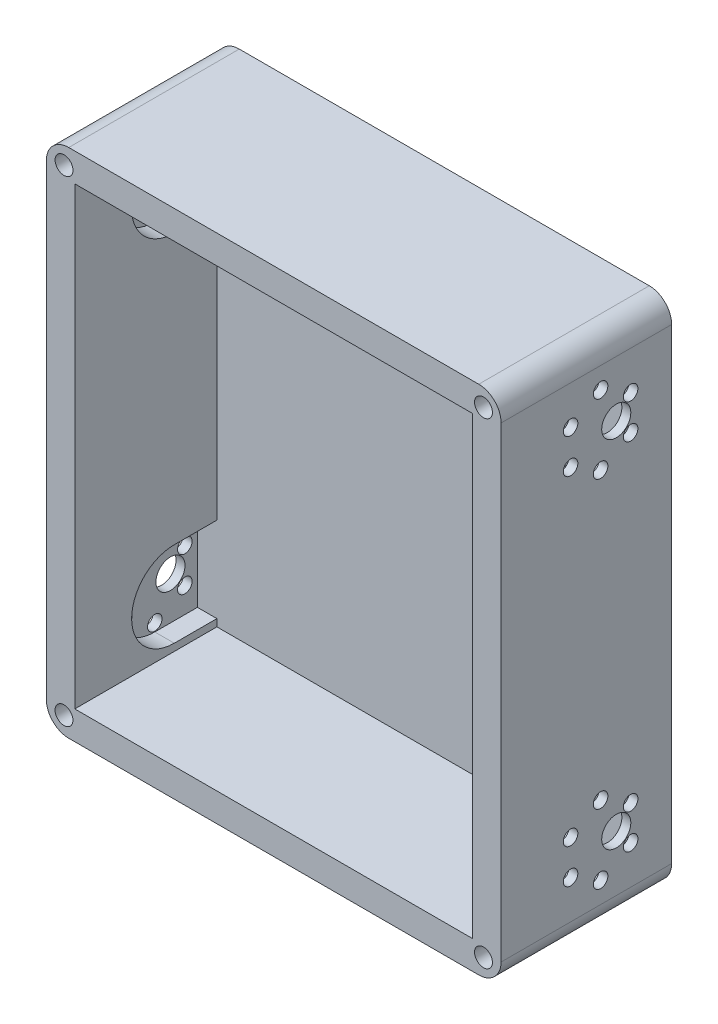
SolidWorks part; units mm, degrees
material "ABS"
ref_plane "Front Plane" through (0, 0, 0) normal (0, 0, 1) x (1, 0, 0)
ref_plane "Top Plane" through (0, 0, 0) normal (0, 1, 0) x (1, 0, 0)
ref_plane "Right Plane" through (0, 0, 0) normal (1, 0, 0) x (0, 0, -1)
sketch "Sketch1" plane through (0, 0, 0) normal (0, 0, 1) x (1, 0, 0)
  line L1 (-106.7309, 50.6092) -> (96.4691, 50.6092)
  line L2 (-106.7309, 50.6092) -> (-106.7309, -177.9908)
  line L3 (-106.7309, -177.9908) -> (96.4691, -177.9908)
  line L4 (96.4691, 50.6092) -> (96.4691, -177.9908)
  dimension "D1" = 203.2
  dimension "D2" = 228.6
extrude "Chassis" add sketch "Sketch1" along normal blind 76.2
shell "Chassis Compartment" thickness 12.7 removed face at (-5.1309, -63.6908, 76.2)
fillet "Outer Fillets" radius 10 4 edges at (96.4691, 50.6092, 38.1) (-106.7309, 50.6092, 38.1) (-106.7309, -177.9908, 38.1) (96.4691, -177.9908, 38.1)
ref_plane "Bottom Plane - Inner" through (0, 0, 12.7) normal (0, 0, 1) x (1, 0, 0)
sketch "Sketch2" plane through (0, 0, 12.7) normal (0, 0, 1) x (1, 0, 0)
  line L0 (-307.7698, 96.8742) -> (-323.3628, 77.6984)
  line L1 (-323.3628, 77.6984) -> (-308.8421, 57.6984)
  line L2 (-308.8421, 57.6984) -> (-293.2492, 76.8742)
  line L3 (-293.2492, 76.8742) -> (-307.7698, 96.8742)
  line L4 (-267.7698, 96.8742) -> (-283.3628, 77.6984)
  line L5 (-283.3628, 77.6984) -> (-268.8421, 57.6984)
  line L6 (-268.8421, 57.6984) -> (-253.2492, 76.8742)
  line L7 (-253.2492, 76.8742) -> (-267.7698, 96.8742)
  line L8 (-227.7698, 96.8742) -> (-243.3628, 77.6984)
  line L9 (-243.3628, 77.6984) -> (-228.8421, 57.6984)
  line L10 (-228.8421, 57.6984) -> (-213.2492, 76.8742)
  line L11 (-213.2492, 76.8742) -> (-227.7698, 96.8742)
  line L12 (-187.7698, 96.8742) -> (-203.3628, 77.6984)
  line L13 (-203.3628, 77.6984) -> (-188.8421, 57.6984)
  line L14 (-188.8421, 57.6984) -> (-173.2492, 76.8742)
  line L15 (-173.2492, 76.8742) -> (-187.7698, 96.8742)
  line L16 (-147.7698, 96.8742) -> (-163.3628, 77.6984)
  line L17 (-163.3628, 77.6984) -> (-148.8421, 57.6984)
  line L18 (-148.8421, 57.6984) -> (-133.2492, 76.8742)
  line L19 (-133.2492, 76.8742) -> (-147.7698, 96.8742)
  line L20 (-107.7698, 96.8742) -> (-123.3628, 77.6984)
  line L21 (-123.3628, 77.6984) -> (-108.8421, 57.6984)
  line L22 (-108.8421, 57.6984) -> (-93.2492, 76.8742)
  line L23 (-93.2492, 76.8742) -> (-107.7698, 96.8742)
  line L24 (-67.7698, 96.8742) -> (-83.3628, 77.6984)
  line L25 (-83.3628, 77.6984) -> (-68.8421, 57.6984)
  line L26 (-68.8421, 57.6984) -> (-53.2492, 76.8742)
  line L27 (-53.2492, 76.8742) -> (-67.7698, 96.8742)
  line L28 (-27.7698, 96.8742) -> (-43.3628, 77.6984)
  line L29 (-43.3628, 77.6984) -> (-28.8421, 57.6984)
  line L30 (-28.8421, 57.6984) -> (-13.2492, 76.8742)
  line L31 (-13.2492, 76.8742) -> (-27.7698, 96.8742)
  line L32 (12.2302, 96.8742) -> (-3.3628, 77.6984)
  line L33 (-3.3628, 77.6984) -> (11.1579, 57.6984)
  line L34 (11.1579, 57.6984) -> (26.7508, 76.8742)
  line L35 (26.7508, 76.8742) -> (12.2302, 96.8742)
  line L36 (52.2302, 96.8742) -> (36.6372, 77.6984)
  line L37 (36.6372, 77.6984) -> (51.1579, 57.6984)
  line L38 (51.1579, 57.6984) -> (66.7508, 76.8742)
  line L39 (66.7508, 76.8742) -> (52.2302, 96.8742)
  line L40 (92.2302, 96.8742) -> (76.6372, 77.6984)
  line L41 (76.6372, 77.6984) -> (91.1579, 57.6984)
  line L42 (91.1579, 57.6984) -> (106.7508, 76.8742)
  line L43 (106.7508, 76.8742) -> (92.2302, 96.8742)
  line L44 (132.2302, 96.8742) -> (116.6372, 77.6984)
  line L45 (116.6372, 77.6984) -> (131.1579, 57.6984)
  line L46 (131.1579, 57.6984) -> (146.7508, 76.8742)
  line L47 (146.7508, 76.8742) -> (132.2302, 96.8742)
  line L48 (172.2302, 96.8742) -> (156.6372, 77.6984)
  line L49 (156.6372, 77.6984) -> (171.1579, 57.6984)
  line L50 (171.1579, 57.6984) -> (186.7508, 76.8742)
  line L51 (186.7508, 76.8742) -> (172.2302, 96.8742)
  line L52 (212.2302, 96.8742) -> (196.6372, 77.6984)
  line L53 (196.6372, 77.6984) -> (211.1579, 57.6984)
  line L54 (211.1579, 57.6984) -> (226.7508, 76.8742)
  line L55 (226.7508, 76.8742) -> (212.2302, 96.8742)
  line L56 (252.2302, 96.8742) -> (236.6372, 77.6984)
  line L57 (236.6372, 77.6984) -> (251.1579, 57.6984)
  line L58 (251.1579, 57.6984) -> (266.7508, 76.8742)
  line L59 (266.7508, 76.8742) -> (252.2302, 96.8742)
  line L60 (-245.9843, 63.3274) -> (-261.5772, 44.1516)
  line L61 (-261.5772, 44.1516) -> (-247.0565, 24.1516)
  line L62 (-247.0565, 24.1516) -> (-231.4636, 43.3274)
  line L63 (-231.4636, 43.3274) -> (-245.9843, 63.3274)
  line L64 (-205.9843, 63.3274) -> (-221.5772, 44.1516)
  line L65 (-221.5772, 44.1516) -> (-207.0565, 24.1516)
  line L66 (-207.0565, 24.1516) -> (-191.4636, 43.3274)
  line L67 (-191.4636, 43.3274) -> (-205.9843, 63.3274)
  line L68 (-165.9843, 63.3274) -> (-181.5772, 44.1516)
  line L69 (-181.5772, 44.1516) -> (-167.0565, 24.1516)
  line L70 (-167.0565, 24.1516) -> (-151.4636, 43.3274)
  line L71 (-151.4636, 43.3274) -> (-165.9843, 63.3274)
  line L72 (-125.9843, 63.3274) -> (-141.5772, 44.1516)
  line L73 (-141.5772, 44.1516) -> (-127.0565, 24.1516)
  line L74 (-127.0565, 24.1516) -> (-111.4636, 43.3274)
  line L75 (-111.4636, 43.3274) -> (-125.9843, 63.3274)
  line L76 (-85.9843, 63.3274) -> (-101.5772, 44.1516)
  line L77 (-101.5772, 44.1516) -> (-87.0565, 24.1516)
  line L78 (-87.0565, 24.1516) -> (-71.4636, 43.3274)
  line L79 (-71.4636, 43.3274) -> (-85.9843, 63.3274)
  line L80 (-45.9843, 63.3274) -> (-61.5772, 44.1516)
  line L81 (-61.5772, 44.1516) -> (-47.0565, 24.1516)
  line L82 (-47.0565, 24.1516) -> (-31.4636, 43.3274)
  line L83 (-31.4636, 43.3274) -> (-45.9843, 63.3274)
  line L84 (-5.9843, 63.3274) -> (-21.5772, 44.1516)
  line L85 (-21.5772, 44.1516) -> (-7.0565, 24.1516)
  line L86 (-7.0565, 24.1516) -> (8.5364, 43.3274)
  line L87 (8.5364, 43.3274) -> (-5.9843, 63.3274)
  line L88 (34.0157, 63.3274) -> (18.4228, 44.1516)
  line L89 (18.4228, 44.1516) -> (32.9435, 24.1516)
  line L90 (32.9435, 24.1516) -> (48.5364, 43.3274)
  line L91 (48.5364, 43.3274) -> (34.0157, 63.3274)
  line L92 (74.0157, 63.3274) -> (58.4228, 44.1516)
  line L93 (58.4228, 44.1516) -> (72.9435, 24.1516)
  line L94 (72.9435, 24.1516) -> (88.5364, 43.3274)
  line L95 (88.5364, 43.3274) -> (74.0157, 63.3274)
  line L96 (114.0157, 63.3274) -> (98.4228, 44.1516)
  line L97 (98.4228, 44.1516) -> (112.9435, 24.1516)
  line L98 (112.9435, 24.1516) -> (128.5364, 43.3274)
  line L99 (128.5364, 43.3274) -> (114.0157, 63.3274)
  line L100 (154.0157, 63.3274) -> (138.4228, 44.1516)
  line L101 (138.4228, 44.1516) -> (152.9435, 24.1516)
  line L102 (152.9435, 24.1516) -> (168.5364, 43.3274)
  line L103 (168.5364, 43.3274) -> (154.0157, 63.3274)
  line L104 (194.0157, 63.3274) -> (178.4228, 44.1516)
  line L105 (178.4228, 44.1516) -> (192.9435, 24.1516)
  line L106 (192.9435, 24.1516) -> (208.5364, 43.3274)
  line L107 (208.5364, 43.3274) -> (194.0157, 63.3274)
  line L108 (234.0157, 63.3274) -> (218.4228, 44.1516)
  line L109 (218.4228, 44.1516) -> (232.9435, 24.1516)
  line L110 (232.9435, 24.1516) -> (248.5364, 43.3274)
  line L111 (248.5364, 43.3274) -> (234.0157, 63.3274)
  line L112 (274.0157, 63.3274) -> (258.4228, 44.1516)
  line L113 (258.4228, 44.1516) -> (272.9435, 24.1516)
  line L114 (272.9435, 24.1516) -> (288.5364, 43.3274)
  line L115 (288.5364, 43.3274) -> (274.0157, 63.3274)
  line L116 (-224.1987, 29.7805) -> (-239.7917, 10.6048)
  line L117 (-239.7917, 10.6048) -> (-225.271, -9.3952)
  line L118 (-225.271, -9.3952) -> (-209.678, 9.7805)
  line L119 (-209.678, 9.7805) -> (-224.1987, 29.7805)
  line L120 (-184.1987, 29.7805) -> (-199.7917, 10.6048)
  line L121 (-199.7917, 10.6048) -> (-185.271, -9.3952)
  line L122 (-185.271, -9.3952) -> (-169.678, 9.7805)
  line L123 (-169.678, 9.7805) -> (-184.1987, 29.7805)
  line L124 (-144.1987, 29.7805) -> (-159.7917, 10.6048)
  line L125 (-159.7917, 10.6048) -> (-145.271, -9.3952)
  line L126 (-145.271, -9.3952) -> (-129.678, 9.7805)
  line L127 (-129.678, 9.7805) -> (-144.1987, 29.7805)
  line L128 (-104.1987, 29.7805) -> (-119.7917, 10.6048)
  line L129 (-119.7917, 10.6048) -> (-105.271, -9.3952)
  line L130 (-105.271, -9.3952) -> (-89.678, 9.7805)
  line L131 (-89.678, 9.7805) -> (-104.1987, 29.7805)
  line L132 (-64.1987, 29.7805) -> (-79.7917, 10.6048)
  line L133 (-79.7917, 10.6048) -> (-65.271, -9.3952)
  line L134 (-65.271, -9.3952) -> (-49.678, 9.7805)
  line L135 (-49.678, 9.7805) -> (-64.1987, 29.7805)
  line L136 (-24.1987, 29.7805) -> (-39.7917, 10.6048)
  line L137 (-39.7917, 10.6048) -> (-25.271, -9.3952)
  line L138 (-25.271, -9.3952) -> (-9.678, 9.7805)
  line L139 (-9.678, 9.7805) -> (-24.1987, 29.7805)
  line L140 (15.8013, 29.7805) -> (0.2083, 10.6048)
  line L141 (0.2083, 10.6048) -> (14.729, -9.3952)
  line L142 (14.729, -9.3952) -> (30.322, 9.7805)
  line L143 (30.322, 9.7805) -> (15.8013, 29.7805)
  line L144 (55.8013, 29.7805) -> (40.2083, 10.6048)
  line L145 (40.2083, 10.6048) -> (54.729, -9.3952)
  line L146 (54.729, -9.3952) -> (70.322, 9.7805)
  line L147 (70.322, 9.7805) -> (55.8013, 29.7805)
  line L148 (95.8013, 29.7805) -> (80.2083, 10.6048)
  line L149 (80.2083, 10.6048) -> (94.729, -9.3952)
  line L150 (94.729, -9.3952) -> (110.322, 9.7805)
  line L151 (110.322, 9.7805) -> (95.8013, 29.7805)
  line L152 (135.8013, 29.7805) -> (120.2083, 10.6048)
  line L153 (120.2083, 10.6048) -> (134.729, -9.3952)
  line L154 (134.729, -9.3952) -> (150.322, 9.7805)
  line L155 (150.322, 9.7805) -> (135.8013, 29.7805)
  line L156 (175.8013, 29.7805) -> (160.2083, 10.6048)
  line L157 (160.2083, 10.6048) -> (174.729, -9.3952)
  line L158 (174.729, -9.3952) -> (190.322, 9.7805)
  line L159 (190.322, 9.7805) -> (175.8013, 29.7805)
  line L160 (215.8013, 29.7805) -> (200.2083, 10.6048)
  line L161 (200.2083, 10.6048) -> (214.729, -9.3952)
  line L162 (214.729, -9.3952) -> (230.322, 9.7805)
  line L163 (230.322, 9.7805) -> (215.8013, 29.7805)
  line L164 (255.8013, 29.7805) -> (240.2083, 10.6048)
  line L165 (240.2083, 10.6048) -> (254.729, -9.3952)
  line L166 (254.729, -9.3952) -> (270.322, 9.7805)
  line L167 (270.322, 9.7805) -> (255.8013, 29.7805)
  line L168 (295.8013, 29.7805) -> (280.2083, 10.6048)
  line L169 (280.2083, 10.6048) -> (294.729, -9.3952)
  line L170 (294.729, -9.3952) -> (310.322, 9.7805)
  line L171 (310.322, 9.7805) -> (295.8013, 29.7805)
  line L172 (-202.4132, -3.7663) -> (-218.0061, -22.9421)
  line L173 (-218.0061, -22.9421) -> (-203.4854, -42.9421)
  line L174 (-203.4854, -42.9421) -> (-187.8925, -23.7663)
  line L175 (-187.8925, -23.7663) -> (-202.4132, -3.7663)
  line L176 (-162.4132, -3.7663) -> (-178.0061, -22.9421)
  line L177 (-178.0061, -22.9421) -> (-163.4854, -42.9421)
  line L178 (-163.4854, -42.9421) -> (-147.8925, -23.7663)
  line L179 (-147.8925, -23.7663) -> (-162.4132, -3.7663)
  line L180 (-122.4132, -3.7663) -> (-138.0061, -22.9421)
  line L181 (-138.0061, -22.9421) -> (-123.4854, -42.9421)
  line L182 (-123.4854, -42.9421) -> (-107.8925, -23.7663)
  line L183 (-107.8925, -23.7663) -> (-122.4132, -3.7663)
  line L184 (-82.4132, -3.7663) -> (-98.0061, -22.9421)
  line L185 (-98.0061, -22.9421) -> (-83.4854, -42.9421)
  line L186 (-83.4854, -42.9421) -> (-67.8925, -23.7663)
  line L187 (-67.8925, -23.7663) -> (-82.4132, -3.7663)
  line L188 (-42.4132, -3.7663) -> (-58.0061, -22.9421)
  line L189 (-58.0061, -22.9421) -> (-43.4854, -42.9421)
  line L190 (-43.4854, -42.9421) -> (-27.8925, -23.7663)
  line L191 (-27.8925, -23.7663) -> (-42.4132, -3.7663)
  line L192 (-2.4132, -3.7663) -> (-18.0061, -22.9421)
  line L193 (-18.0061, -22.9421) -> (-3.4854, -42.9421)
  line L194 (-3.4854, -42.9421) -> (12.1075, -23.7663)
  line L195 (12.1075, -23.7663) -> (-2.4132, -3.7663)
  line L196 (37.5868, -3.7663) -> (21.9939, -22.9421)
  line L197 (21.9939, -22.9421) -> (36.5146, -42.9421)
  line L198 (36.5146, -42.9421) -> (52.1075, -23.7663)
  line L199 (52.1075, -23.7663) -> (37.5868, -3.7663)
  line L200 (77.5868, -3.7663) -> (61.9939, -22.9421)
  line L201 (61.9939, -22.9421) -> (76.5146, -42.9421)
  line L202 (76.5146, -42.9421) -> (92.1075, -23.7663)
  line L203 (92.1075, -23.7663) -> (77.5868, -3.7663)
  line L204 (117.5868, -3.7663) -> (101.9939, -22.9421)
  line L205 (101.9939, -22.9421) -> (116.5146, -42.9421)
  line L206 (116.5146, -42.9421) -> (132.1075, -23.7663)
  line L207 (132.1075, -23.7663) -> (117.5868, -3.7663)
  line L208 (157.5868, -3.7663) -> (141.9939, -22.9421)
  line L209 (141.9939, -22.9421) -> (156.5146, -42.9421)
  line L210 (156.5146, -42.9421) -> (172.1075, -23.7663)
  line L211 (172.1075, -23.7663) -> (157.5868, -3.7663)
  line L212 (197.5868, -3.7663) -> (181.9939, -22.9421)
  line L213 (181.9939, -22.9421) -> (196.5146, -42.9421)
  line L214 (196.5146, -42.9421) -> (212.1075, -23.7663)
  line L215 (212.1075, -23.7663) -> (197.5868, -3.7663)
  line L216 (237.5868, -3.7663) -> (221.9939, -22.9421)
  line L217 (221.9939, -22.9421) -> (236.5146, -42.9421)
  line L218 (236.5146, -42.9421) -> (252.1075, -23.7663)
  line L219 (252.1075, -23.7663) -> (237.5868, -3.7663)
  line L220 (277.5868, -3.7663) -> (261.9939, -22.9421)
  line L221 (261.9939, -22.9421) -> (276.5146, -42.9421)
  line L222 (276.5146, -42.9421) -> (292.1075, -23.7663)
  line L223 (292.1075, -23.7663) -> (277.5868, -3.7663)
  line L224 (317.5868, -3.7663) -> (301.9939, -22.9421)
  line L225 (301.9939, -22.9421) -> (316.5146, -42.9421)
  line L226 (316.5146, -42.9421) -> (332.1075, -23.7663)
  line L227 (332.1075, -23.7663) -> (317.5868, -3.7663)
  line L228 (-180.6276, -37.3131) -> (-196.2206, -56.4889)
  line L229 (-196.2206, -56.4889) -> (-181.6999, -76.4889)
  line L230 (-181.6999, -76.4889) -> (-166.1069, -57.3131)
  line L231 (-166.1069, -57.3131) -> (-180.6276, -37.3131)
  line L232 (-140.6276, -37.3131) -> (-156.2206, -56.4889)
  line L233 (-156.2206, -56.4889) -> (-141.6999, -76.4889)
  line L234 (-141.6999, -76.4889) -> (-126.1069, -57.3131)
  line L235 (-126.1069, -57.3131) -> (-140.6276, -37.3131)
  line L236 (-100.6276, -37.3131) -> (-116.2206, -56.4889)
  line L237 (-116.2206, -56.4889) -> (-101.6999, -76.4889)
  line L238 (-101.6999, -76.4889) -> (-86.1069, -57.3131)
  line L239 (-86.1069, -57.3131) -> (-100.6276, -37.3131)
  line L240 (-60.6276, -37.3131) -> (-76.2206, -56.4889)
  line L241 (-76.2206, -56.4889) -> (-61.6999, -76.4889)
  line L242 (-61.6999, -76.4889) -> (-46.1069, -57.3131)
  line L243 (-46.1069, -57.3131) -> (-60.6276, -37.3131)
  line L244 (-20.6276, -37.3131) -> (-36.2206, -56.4889)
  line L245 (-36.2206, -56.4889) -> (-21.6999, -76.4889)
  line L246 (-21.6999, -76.4889) -> (-6.1069, -57.3131)
  line L247 (-6.1069, -57.3131) -> (-20.6276, -37.3131)
  line L248 (19.3724, -37.3131) -> (3.7794, -56.4889)
  line L249 (3.7794, -56.4889) -> (18.3001, -76.4889)
  line L250 (18.3001, -76.4889) -> (33.8931, -57.3131)
  line L251 (33.8931, -57.3131) -> (19.3724, -37.3131)
  line L252 (59.3724, -37.3131) -> (43.7794, -56.4889)
  line L253 (43.7794, -56.4889) -> (58.3001, -76.4889)
  line L254 (58.3001, -76.4889) -> (73.8931, -57.3131)
  line L255 (73.8931, -57.3131) -> (59.3724, -37.3131)
  line L256 (99.3724, -37.3131) -> (83.7794, -56.4889)
  line L257 (83.7794, -56.4889) -> (98.3001, -76.4889)
  line L258 (98.3001, -76.4889) -> (113.8931, -57.3131)
  line L259 (113.8931, -57.3131) -> (99.3724, -37.3131)
  line L260 (139.3724, -37.3131) -> (123.7794, -56.4889)
  line L261 (123.7794, -56.4889) -> (138.3001, -76.4889)
  line L262 (138.3001, -76.4889) -> (153.8931, -57.3131)
  line L263 (153.8931, -57.3131) -> (139.3724, -37.3131)
  line L264 (179.3724, -37.3131) -> (163.7794, -56.4889)
  line L265 (163.7794, -56.4889) -> (178.3001, -76.4889)
  line L266 (178.3001, -76.4889) -> (193.8931, -57.3131)
  line L267 (193.8931, -57.3131) -> (179.3724, -37.3131)
  line L268 (219.3724, -37.3131) -> (203.7794, -56.4889)
  line L269 (203.7794, -56.4889) -> (218.3001, -76.4889)
  line L270 (218.3001, -76.4889) -> (233.8931, -57.3131)
  line L271 (233.8931, -57.3131) -> (219.3724, -37.3131)
  line L272 (259.3724, -37.3131) -> (243.7794, -56.4889)
  line L273 (243.7794, -56.4889) -> (258.3001, -76.4889)
  line L274 (258.3001, -76.4889) -> (273.8931, -57.3131)
  line L275 (273.8931, -57.3131) -> (259.3724, -37.3131)
  line L276 (299.3724, -37.3131) -> (283.7794, -56.4889)
  line L277 (283.7794, -56.4889) -> (298.3001, -76.4889)
  line L278 (298.3001, -76.4889) -> (313.8931, -57.3131)
  line L279 (313.8931, -57.3131) -> (299.3724, -37.3131)
  line L280 (339.3724, -37.3131) -> (323.7794, -56.4889)
  line L281 (323.7794, -56.4889) -> (338.3001, -76.4889)
  line L282 (338.3001, -76.4889) -> (353.8931, -57.3131)
  line L283 (353.8931, -57.3131) -> (339.3724, -37.3131)
  line L284 (-158.842, -70.8599) -> (-174.435, -90.0357)
  line L285 (-174.435, -90.0357) -> (-159.9143, -110.0357)
  line L286 (-159.9143, -110.0357) -> (-144.3213, -90.8599)
  line L287 (-144.3213, -90.8599) -> (-158.842, -70.8599)
  line L288 (-118.842, -70.8599) -> (-134.435, -90.0357)
  line L289 (-134.435, -90.0357) -> (-119.9143, -110.0357)
  line L290 (-119.9143, -110.0357) -> (-104.3213, -90.8599)
  line L291 (-104.3213, -90.8599) -> (-118.842, -70.8599)
  line L292 (-78.842, -70.8599) -> (-94.435, -90.0357)
  line L293 (-94.435, -90.0357) -> (-79.9143, -110.0357)
  line L294 (-79.9143, -110.0357) -> (-64.3213, -90.8599)
  line L295 (-64.3213, -90.8599) -> (-78.842, -70.8599)
  line L296 (-38.842, -70.8599) -> (-54.435, -90.0357)
  line L297 (-54.435, -90.0357) -> (-39.9143, -110.0357)
  line L298 (-39.9143, -110.0357) -> (-24.3213, -90.8599)
  line L299 (-24.3213, -90.8599) -> (-38.842, -70.8599)
  line L300 (1.158, -70.8599) -> (-14.435, -90.0357)
  line L301 (-14.435, -90.0357) -> (0.0857, -110.0357)
  line L302 (0.0857, -110.0357) -> (15.6787, -90.8599)
  line L303 (15.6787, -90.8599) -> (1.158, -70.8599)
  line L304 (41.158, -70.8599) -> (25.565, -90.0357)
  line L305 (25.565, -90.0357) -> (40.0857, -110.0357)
  line L306 (40.0857, -110.0357) -> (55.6787, -90.8599)
  line L307 (55.6787, -90.8599) -> (41.158, -70.8599)
  line L308 (81.158, -70.8599) -> (65.565, -90.0357)
  line L309 (65.565, -90.0357) -> (80.0857, -110.0357)
  line L310 (80.0857, -110.0357) -> (95.6787, -90.8599)
  line L311 (95.6787, -90.8599) -> (81.158, -70.8599)
  line L312 (121.158, -70.8599) -> (105.565, -90.0357)
  line L313 (105.565, -90.0357) -> (120.0857, -110.0357)
  line L314 (120.0857, -110.0357) -> (135.6787, -90.8599)
  line L315 (135.6787, -90.8599) -> (121.158, -70.8599)
  line L316 (161.158, -70.8599) -> (145.565, -90.0357)
  line L317 (145.565, -90.0357) -> (160.0857, -110.0357)
  line L318 (160.0857, -110.0357) -> (175.6787, -90.8599)
  line L319 (175.6787, -90.8599) -> (161.158, -70.8599)
  line L320 (201.158, -70.8599) -> (185.565, -90.0357)
  line L321 (185.565, -90.0357) -> (200.0857, -110.0357)
  line L322 (200.0857, -110.0357) -> (215.6787, -90.8599)
  line L323 (215.6787, -90.8599) -> (201.158, -70.8599)
  line L324 (241.158, -70.8599) -> (225.565, -90.0357)
  line L325 (225.565, -90.0357) -> (240.0857, -110.0357)
  line L326 (240.0857, -110.0357) -> (255.6787, -90.8599)
  line L327 (255.6787, -90.8599) -> (241.158, -70.8599)
  line L328 (281.158, -70.8599) -> (265.565, -90.0357)
  line L329 (265.565, -90.0357) -> (280.0857, -110.0357)
  line L330 (280.0857, -110.0357) -> (295.6787, -90.8599)
  line L331 (295.6787, -90.8599) -> (281.158, -70.8599)
  line L332 (321.158, -70.8599) -> (305.565, -90.0357)
  line L333 (305.565, -90.0357) -> (320.0857, -110.0357)
  line L334 (320.0857, -110.0357) -> (335.6787, -90.8599)
  line L335 (335.6787, -90.8599) -> (321.158, -70.8599)
  line L336 (361.158, -70.8599) -> (345.565, -90.0357)
  line L337 (345.565, -90.0357) -> (360.0857, -110.0357)
  line L338 (360.0857, -110.0357) -> (375.6787, -90.8599)
  line L339 (375.6787, -90.8599) -> (361.158, -70.8599)
  line L340 (-137.0565, -104.4068) -> (-152.6494, -123.5825)
  line L341 (-152.6494, -123.5825) -> (-138.1287, -143.5825)
  line L342 (-138.1287, -143.5825) -> (-122.5358, -124.4068)
  line L343 (-122.5358, -124.4068) -> (-137.0565, -104.4068)
  line L344 (-97.0565, -104.4068) -> (-112.6494, -123.5825)
  line L345 (-112.6494, -123.5825) -> (-98.1287, -143.5825)
  line L346 (-98.1287, -143.5825) -> (-82.5358, -124.4068)
  line L347 (-82.5358, -124.4068) -> (-97.0565, -104.4068)
  line L348 (-57.0565, -104.4068) -> (-72.6494, -123.5825)
  line L349 (-72.6494, -123.5825) -> (-58.1287, -143.5825)
  line L350 (-58.1287, -143.5825) -> (-42.5358, -124.4068)
  line L351 (-42.5358, -124.4068) -> (-57.0565, -104.4068)
  line L352 (-17.0565, -104.4068) -> (-32.6494, -123.5825)
  line L353 (-32.6494, -123.5825) -> (-18.1287, -143.5825)
  line L354 (-18.1287, -143.5825) -> (-2.5358, -124.4068)
  line L355 (-2.5358, -124.4068) -> (-17.0565, -104.4068)
  line L356 (22.9435, -104.4068) -> (7.3506, -123.5825)
  line L357 (7.3506, -123.5825) -> (21.8713, -143.5825)
  line L358 (21.8713, -143.5825) -> (37.4642, -124.4068)
  line L359 (37.4642, -124.4068) -> (22.9435, -104.4068)
  line L360 (62.9435, -104.4068) -> (47.3506, -123.5825)
  line L361 (47.3506, -123.5825) -> (61.8713, -143.5825)
  line L362 (61.8713, -143.5825) -> (77.4642, -124.4068)
  line L363 (77.4642, -124.4068) -> (62.9435, -104.4068)
  line L364 (102.9435, -104.4068) -> (87.3506, -123.5825)
  line L365 (87.3506, -123.5825) -> (101.8713, -143.5825)
  line L366 (101.8713, -143.5825) -> (117.4642, -124.4068)
  line L367 (117.4642, -124.4068) -> (102.9435, -104.4068)
  line L368 (142.9435, -104.4068) -> (127.3506, -123.5825)
  line L369 (127.3506, -123.5825) -> (141.8713, -143.5825)
  line L370 (141.8713, -143.5825) -> (157.4642, -124.4068)
  line L371 (157.4642, -124.4068) -> (142.9435, -104.4068)
  line L372 (182.9435, -104.4068) -> (167.3506, -123.5825)
  line L373 (167.3506, -123.5825) -> (181.8713, -143.5825)
  line L374 (181.8713, -143.5825) -> (197.4642, -124.4068)
  line L375 (197.4642, -124.4068) -> (182.9435, -104.4068)
  line L376 (222.9435, -104.4068) -> (207.3506, -123.5825)
  line L377 (207.3506, -123.5825) -> (221.8713, -143.5825)
  line L378 (221.8713, -143.5825) -> (237.4642, -124.4068)
  line L379 (237.4642, -124.4068) -> (222.9435, -104.4068)
  line L380 (262.9435, -104.4068) -> (247.3506, -123.5825)
  line L381 (247.3506, -123.5825) -> (261.8713, -143.5825)
  line L382 (261.8713, -143.5825) -> (277.4642, -124.4068)
  line L383 (277.4642, -124.4068) -> (262.9435, -104.4068)
  line L384 (302.9435, -104.4068) -> (287.3506, -123.5825)
  line L385 (287.3506, -123.5825) -> (301.8713, -143.5825)
  line L386 (301.8713, -143.5825) -> (317.4642, -124.4068)
  line L387 (317.4642, -124.4068) -> (302.9435, -104.4068)
  line L388 (342.9435, -104.4068) -> (327.3506, -123.5825)
  line L389 (327.3506, -123.5825) -> (341.8713, -143.5825)
  line L390 (341.8713, -143.5825) -> (357.4642, -124.4068)
  line L391 (357.4642, -124.4068) -> (342.9435, -104.4068)
  line L392 (382.9435, -104.4068) -> (367.3506, -123.5825)
  line L393 (367.3506, -123.5825) -> (381.8713, -143.5825)
  line L394 (381.8713, -143.5825) -> (397.4642, -124.4068)
  line L395 (397.4642, -124.4068) -> (382.9435, -104.4068)
  line L396 (-115.2709, -137.9536) -> (-130.8639, -157.1294)
  line L397 (-130.8639, -157.1294) -> (-116.3432, -177.1294)
  line L398 (-116.3432, -177.1294) -> (-100.7502, -157.9536)
  line L399 (-100.7502, -157.9536) -> (-115.2709, -137.9536)
  line L400 (-75.2709, -137.9536) -> (-90.8639, -157.1294)
  line L401 (-90.8639, -157.1294) -> (-76.3432, -177.1294)
  line L402 (-76.3432, -177.1294) -> (-60.7502, -157.9536)
  line L403 (-60.7502, -157.9536) -> (-75.2709, -137.9536)
  line L404 (-35.2709, -137.9536) -> (-50.8639, -157.1294)
  line L405 (-50.8639, -157.1294) -> (-36.3432, -177.1294)
  line L406 (-36.3432, -177.1294) -> (-20.7502, -157.9536)
  line L407 (-20.7502, -157.9536) -> (-35.2709, -137.9536)
  line L408 (4.7291, -137.9536) -> (-10.8639, -157.1294)
  line L409 (-10.8639, -157.1294) -> (3.6568, -177.1294)
  line L410 (3.6568, -177.1294) -> (19.2498, -157.9536)
  line L411 (19.2498, -157.9536) -> (4.7291, -137.9536)
  line L412 (44.7291, -137.9536) -> (29.1361, -157.1294)
  line L413 (29.1361, -157.1294) -> (43.6568, -177.1294)
  line L414 (43.6568, -177.1294) -> (59.2498, -157.9536)
  line L415 (59.2498, -157.9536) -> (44.7291, -137.9536)
  line L416 (84.7291, -137.9536) -> (69.1361, -157.1294)
  line L417 (69.1361, -157.1294) -> (83.6568, -177.1294)
  line L418 (83.6568, -177.1294) -> (99.2498, -157.9536)
  line L419 (99.2498, -157.9536) -> (84.7291, -137.9536)
  line L420 (124.7291, -137.9536) -> (109.1361, -157.1294)
  line L421 (109.1361, -157.1294) -> (123.6568, -177.1294)
  line L422 (123.6568, -177.1294) -> (139.2498, -157.9536)
  line L423 (139.2498, -157.9536) -> (124.7291, -137.9536)
  line L424 (164.7291, -137.9536) -> (149.1361, -157.1294)
  line L425 (149.1361, -157.1294) -> (163.6568, -177.1294)
  line L426 (163.6568, -177.1294) -> (179.2498, -157.9536)
  line L427 (179.2498, -157.9536) -> (164.7291, -137.9536)
  line L428 (204.7291, -137.9536) -> (189.1361, -157.1294)
  line L429 (189.1361, -157.1294) -> (203.6568, -177.1294)
  line L430 (203.6568, -177.1294) -> (219.2498, -157.9536)
  line L431 (219.2498, -157.9536) -> (204.7291, -137.9536)
  line L432 (244.7291, -137.9536) -> (229.1361, -157.1294)
  line L433 (229.1361, -157.1294) -> (243.6568, -177.1294)
  line L434 (243.6568, -177.1294) -> (259.2498, -157.9536)
  line L435 (259.2498, -157.9536) -> (244.7291, -137.9536)
  line L436 (284.7291, -137.9536) -> (269.1361, -157.1294)
  line L437 (269.1361, -157.1294) -> (283.6568, -177.1294)
  line L438 (283.6568, -177.1294) -> (299.2498, -157.9536)
  line L439 (299.2498, -157.9536) -> (284.7291, -137.9536)
  line L440 (324.7291, -137.9536) -> (309.1361, -157.1294)
  line L441 (309.1361, -157.1294) -> (323.6568, -177.1294)
  line L442 (323.6568, -177.1294) -> (339.2498, -157.9536)
  line L443 (339.2498, -157.9536) -> (324.7291, -137.9536)
  line L444 (364.7291, -137.9536) -> (349.1361, -157.1294)
  line L445 (349.1361, -157.1294) -> (363.6568, -177.1294)
  line L446 (363.6568, -177.1294) -> (379.2498, -157.9536)
  line L447 (379.2498, -157.9536) -> (364.7291, -137.9536)
  line L448 (404.7291, -137.9536) -> (389.1361, -157.1294)
  line L449 (389.1361, -157.1294) -> (403.6568, -177.1294)
  line L450 (403.6568, -177.1294) -> (419.2498, -157.9536)
  line L451 (419.2498, -157.9536) -> (404.7291, -137.9536)
  line L452 (-93.4854, -171.5004) -> (-109.0783, -190.6762)
  line L453 (-109.0783, -190.6762) -> (-94.5576, -210.6762)
  line L454 (-94.5576, -210.6762) -> (-78.9647, -191.5004)
  line L455 (-78.9647, -191.5004) -> (-93.4854, -171.5004)
  line L456 (-53.4854, -171.5004) -> (-69.0783, -190.6762)
  line L457 (-69.0783, -190.6762) -> (-54.5576, -210.6762)
  line L458 (-54.5576, -210.6762) -> (-38.9647, -191.5004)
  line L459 (-38.9647, -191.5004) -> (-53.4854, -171.5004)
  line L460 (-13.4854, -171.5004) -> (-29.0783, -190.6762)
  line L461 (-29.0783, -190.6762) -> (-14.5576, -210.6762)
  line L462 (-14.5576, -210.6762) -> (1.0353, -191.5004)
  line L463 (1.0353, -191.5004) -> (-13.4854, -171.5004)
  line L464 (26.5146, -171.5004) -> (10.9217, -190.6762)
  line L465 (10.9217, -190.6762) -> (25.4424, -210.6762)
  line L466 (25.4424, -210.6762) -> (41.0353, -191.5004)
  line L467 (41.0353, -191.5004) -> (26.5146, -171.5004)
  line L468 (66.5146, -171.5004) -> (50.9217, -190.6762)
  line L469 (50.9217, -190.6762) -> (65.4424, -210.6762)
  line L470 (65.4424, -210.6762) -> (81.0353, -191.5004)
  line L471 (81.0353, -191.5004) -> (66.5146, -171.5004)
  line L472 (106.5146, -171.5004) -> (90.9217, -190.6762)
  line L473 (90.9217, -190.6762) -> (105.4424, -210.6762)
  line L474 (105.4424, -210.6762) -> (121.0353, -191.5004)
  line L475 (121.0353, -191.5004) -> (106.5146, -171.5004)
  line L476 (146.5146, -171.5004) -> (130.9217, -190.6762)
  line L477 (130.9217, -190.6762) -> (145.4424, -210.6762)
  line L478 (145.4424, -210.6762) -> (161.0353, -191.5004)
  line L479 (161.0353, -191.5004) -> (146.5146, -171.5004)
  line L480 (186.5146, -171.5004) -> (170.9217, -190.6762)
  line L481 (170.9217, -190.6762) -> (185.4424, -210.6762)
  line L482 (185.4424, -210.6762) -> (201.0353, -191.5004)
  line L483 (201.0353, -191.5004) -> (186.5146, -171.5004)
  line L484 (226.5146, -171.5004) -> (210.9217, -190.6762)
  line L485 (210.9217, -190.6762) -> (225.4424, -210.6762)
  line L486 (225.4424, -210.6762) -> (241.0353, -191.5004)
  line L487 (241.0353, -191.5004) -> (226.5146, -171.5004)
  line L488 (266.5146, -171.5004) -> (250.9217, -190.6762)
  line L489 (250.9217, -190.6762) -> (265.4424, -210.6762)
  line L490 (265.4424, -210.6762) -> (281.0353, -191.5004)
  line L491 (281.0353, -191.5004) -> (266.5146, -171.5004)
  line L492 (306.5146, -171.5004) -> (290.9217, -190.6762)
  line L493 (290.9217, -190.6762) -> (305.4424, -210.6762)
  line L494 (305.4424, -210.6762) -> (321.0353, -191.5004)
  line L495 (321.0353, -191.5004) -> (306.5146, -171.5004)
  line L496 (346.5146, -171.5004) -> (330.9217, -190.6762)
  line L497 (330.9217, -190.6762) -> (345.4424, -210.6762)
  line L498 (345.4424, -210.6762) -> (361.0353, -191.5004)
  line L499 (361.0353, -191.5004) -> (346.5146, -171.5004)
  line L500 (386.5146, -171.5004) -> (370.9217, -190.6762)
  line L501 (370.9217, -190.6762) -> (385.4424, -210.6762)
  line L502 (385.4424, -210.6762) -> (401.0353, -191.5004)
  line L503 (401.0353, -191.5004) -> (386.5146, -171.5004)
  line L504 (426.5146, -171.5004) -> (410.9217, -190.6762)
  line L505 (410.9217, -190.6762) -> (425.4424, -210.6762)
  line L506 (425.4424, -210.6762) -> (441.0353, -191.5004)
  line L507 (441.0353, -191.5004) -> (426.5146, -171.5004)
  line L508 (-71.6998, -205.0472) -> (-87.2928, -224.223)
  line L509 (-87.2928, -224.223) -> (-72.7721, -244.223)
  line L510 (-72.7721, -244.223) -> (-57.1791, -225.0472)
  line L511 (-57.1791, -225.0472) -> (-71.6998, -205.0472)
  line L512 (-31.6998, -205.0472) -> (-47.2928, -224.223)
  line L513 (-47.2928, -224.223) -> (-32.7721, -244.223)
  line L514 (-32.7721, -244.223) -> (-17.1791, -225.0472)
  line L515 (-17.1791, -225.0472) -> (-31.6998, -205.0472)
  line L516 (8.3002, -205.0472) -> (-7.2928, -224.223)
  line L517 (-7.2928, -224.223) -> (7.2279, -244.223)
  line L518 (7.2279, -244.223) -> (22.8209, -225.0472)
  line L519 (22.8209, -225.0472) -> (8.3002, -205.0472)
  line L520 (48.3002, -205.0472) -> (32.7072, -224.223)
  line L521 (32.7072, -224.223) -> (47.2279, -244.223)
  line L522 (47.2279, -244.223) -> (62.8209, -225.0472)
  line L523 (62.8209, -225.0472) -> (48.3002, -205.0472)
  line L524 (88.3002, -205.0472) -> (72.7072, -224.223)
  line L525 (72.7072, -224.223) -> (87.2279, -244.223)
  line L526 (87.2279, -244.223) -> (102.8209, -225.0472)
  line L527 (102.8209, -225.0472) -> (88.3002, -205.0472)
  line L528 (128.3002, -205.0472) -> (112.7072, -224.223)
  line L529 (112.7072, -224.223) -> (127.2279, -244.223)
  line L530 (127.2279, -244.223) -> (142.8209, -225.0472)
  line L531 (142.8209, -225.0472) -> (128.3002, -205.0472)
  line L532 (168.3002, -205.0472) -> (152.7072, -224.223)
  line L533 (152.7072, -224.223) -> (167.2279, -244.223)
  line L534 (167.2279, -244.223) -> (182.8209, -225.0472)
  line L535 (182.8209, -225.0472) -> (168.3002, -205.0472)
  line L536 (208.3002, -205.0472) -> (192.7072, -224.223)
  line L537 (192.7072, -224.223) -> (207.2279, -244.223)
  line L538 (207.2279, -244.223) -> (222.8209, -225.0472)
  line L539 (222.8209, -225.0472) -> (208.3002, -205.0472)
  line L540 (248.3002, -205.0472) -> (232.7072, -224.223)
  line L541 (232.7072, -224.223) -> (247.2279, -244.223)
  line L542 (247.2279, -244.223) -> (262.8209, -225.0472)
  line L543 (262.8209, -225.0472) -> (248.3002, -205.0472)
  line L544 (288.3002, -205.0472) -> (272.7072, -224.223)
  line L545 (272.7072, -224.223) -> (287.2279, -244.223)
  line L546 (287.2279, -244.223) -> (302.8209, -225.0472)
  line L547 (302.8209, -225.0472) -> (288.3002, -205.0472)
  line L548 (328.3002, -205.0472) -> (312.7072, -224.223)
  line L549 (312.7072, -224.223) -> (327.2279, -244.223)
  line L550 (327.2279, -244.223) -> (342.8209, -225.0472)
  line L551 (342.8209, -225.0472) -> (328.3002, -205.0472)
  line L552 (368.3002, -205.0472) -> (352.7072, -224.223)
  line L553 (352.7072, -224.223) -> (367.2279, -244.223)
  line L554 (367.2279, -244.223) -> (382.8209, -225.0472)
  line L555 (382.8209, -225.0472) -> (368.3002, -205.0472)
  line L556 (408.3002, -205.0472) -> (392.7072, -224.223)
  line L557 (392.7072, -224.223) -> (407.2279, -244.223)
  line L558 (407.2279, -244.223) -> (422.8209, -225.0472)
  line L559 (422.8209, -225.0472) -> (408.3002, -205.0472)
  line L560 (448.3002, -205.0472) -> (432.7072, -224.223)
  line L561 (432.7072, -224.223) -> (447.2279, -244.223)
  line L562 (447.2279, -244.223) -> (462.8209, -225.0472)
  line L563 (462.8209, -225.0472) -> (448.3002, -205.0472)
  line L564 (-285.9843, 63.3274) -> (-301.5772, 44.1516)
  line L565 (-301.5772, 44.1516) -> (-287.0565, 24.1516)
  line L566 (-287.0565, 24.1516) -> (-271.4636, 43.3274)
  line L567 (-271.4636, 43.3274) -> (-285.9843, 63.3274)
  line L568 (-264.1987, 29.7805) -> (-279.7917, 10.6048)
  line L569 (-279.7917, 10.6048) -> (-265.271, -9.3952)
  line L570 (-265.271, -9.3952) -> (-249.678, 9.7805)
  line L571 (-249.678, 9.7805) -> (-264.1987, 29.7805)
  line L572 (-242.4132, -3.7663) -> (-258.0061, -22.9421)
  line L573 (-258.0061, -22.9421) -> (-243.4854, -42.9421)
  line L574 (-243.4854, -42.9421) -> (-227.8925, -23.7663)
  line L575 (-227.8925, -23.7663) -> (-242.4132, -3.7663)
  line L576 (-220.6276, -37.3131) -> (-236.2206, -56.4889)
  line L577 (-236.2206, -56.4889) -> (-221.6999, -76.4889)
  line L578 (-221.6999, -76.4889) -> (-206.1069, -57.3131)
  line L579 (-206.1069, -57.3131) -> (-220.6276, -37.3131)
  line L580 (-198.842, -70.8599) -> (-214.435, -90.0357)
  line L581 (-214.435, -90.0357) -> (-199.9143, -110.0357)
  line L582 (-199.9143, -110.0357) -> (-184.3213, -90.8599)
  line L583 (-184.3213, -90.8599) -> (-198.842, -70.8599)
  line L584 (-177.0565, -104.4068) -> (-192.6494, -123.5825)
  line L585 (-192.6494, -123.5825) -> (-178.1287, -143.5825)
  line L586 (-178.1287, -143.5825) -> (-162.5358, -124.4068)
  line L587 (-162.5358, -124.4068) -> (-177.0565, -104.4068)
  line L588 (-155.2709, -137.9536) -> (-170.8639, -157.1294)
  line L589 (-170.8639, -157.1294) -> (-156.3432, -177.1294)
  line L590 (-156.3432, -177.1294) -> (-140.7502, -157.9536)
  line L591 (-140.7502, -157.9536) -> (-155.2709, -137.9536)
  line L592 (-133.4854, -171.5004) -> (-149.0783, -190.6762)
  line L593 (-149.0783, -190.6762) -> (-134.5576, -210.6762)
  line L594 (-134.5576, -210.6762) -> (-118.9647, -191.5004)
  line L595 (-118.9647, -191.5004) -> (-133.4854, -171.5004)
  line L596 (-111.6998, -205.0472) -> (-127.2928, -224.223)
  line L597 (-127.2928, -224.223) -> (-112.7721, -244.223)
  line L598 (-112.7721, -244.223) -> (-97.1791, -225.0472)
  line L599 (-97.1791, -225.0472) -> (-111.6998, -205.0472)
  line L600 (-307.7698, 96.8742) -> (-267.7698, 96.8742) construction
  dimension "D1" = 15
  dimension "D2" = 10
  dimension "D3" = 40
extrude "Diamond Cut-Outs" [suppressed] cut sketch "Sketch2" against normal blind 32.54
ref_plane "Left Plane - Inner" through (-94.0309, 0, 0) normal (-1, 0, 0) x (0, 0, 1)
sketch "Sketch3" plane through (-94.0309, 0, 0) normal (-1, 0, 0) x (0, 0, 1)
  line L0 (0, 40.6092) -> (76.2, 40.6092) construction
  line L1 (31.75, -162.0908) -> (12.7, -162.0908)
  line L2 (12.7, -162.0908) -> (12.7, -123.9908)
  line L3 (12.7, -97.79) -> (12.7, 97.79) construction
  line L4 (12.7, -123.9908) -> (31.75, -123.9908)
  line L5 (31.75, -3.3908) -> (12.7, -3.3908)
  line L6 (12.7, -3.3908) -> (12.7, 34.7092)
  line L7 (12.7, 34.7092) -> (31.75, 34.7092)
  arc A0 (31.75, -162.0908) -> (31.75, -123.9908) centre (31.75, -143.0408) ccw
  arc A1 (31.75, -3.3908) -> (31.75, 34.7092) centre (31.75, 15.6592) ccw
  dimension "D1" = 158.7
  dimension "D3" = 38.1
  dimension "D2" = 24.95
extrude "Left Motor Compartments" cut sketch "Sketch3" along normal blind 8.7
ref_plane "Right Plane - Inner" through (83.7691, 0, 0) normal (-1, 0, 0) x (0, 0, 1)
sketch "Sketch5" plane through (83.7691, 0, 0) normal (-1, 0, 0) x (0, 0, 1)
  line L0 (12.7, -102.575) -> (12.7, 102.575) construction
  line L1 (76.2, 40.6092) -> (0, 40.6092) construction
  line L2 (31.75, 34.7092) -> (12.7, 34.7092)
  line L3 (12.7, 34.7092) -> (12.7, -3.3908)
  line L4 (12.7, -3.3908) -> (31.75, -3.3908)
  line L5 (31.75, -123.9908) -> (12.7, -123.9908)
  line L6 (12.7, -123.9908) -> (12.7, -162.0908)
  line L7 (12.7, -162.0908) -> (31.75, -162.0908)
  arc A0 (31.75, -3.3908) -> (31.75, 34.7092) centre (31.75, 15.6592) ccw
  arc A1 (31.75, -162.0908) -> (31.75, -123.9908) centre (31.75, -143.0408) ccw
  dimension "D1" = 120.6
  dimension "D2" = 24.95
extrude "Right Motor Compartments" cut sketch "Sketch5" against normal blind 8.7
ref_plane "Top Plane - Inner" through (0, 0, 76.2) normal (0, 0, 1) x (1, 0, 0)
sketch "Sketch8" plane through (0, 0, 76.2) normal (0, 0, 1) x (1, 0, 0)
  line L0 (93.5402, 47.6802) -> (91.4198, 45.558) construction
  line L1 (-103.802, 47.6802) -> (-101.6797, 45.5598)
  line L2 (93.5402, -175.0619) -> (75.996, -157.5177)
  line L3 (-103.802, -175.0619) -> (-80.996, -152.2559)
  line L4 (-96.0205, 39.9055) -> (-89.8933, 33.7837)
  line L5 (85.7654, 39.8987) -> (83.645, 37.7765) construction
  arc A0 (96.4691, 40.6092) -> (86.4691, 50.6092) centre (86.4691, 40.6092) ccw construction
  arc A1 (-96.7309, 50.6092) -> (-106.7309, 40.6092) centre (-96.7309, 40.6092) ccw construction
  circle A4 centre (88.5904, 42.7305) radius 4
  circle A5 centre (-98.8367, 42.746) radius 4
  arc A6 (86.4691, -177.9908) -> (96.4691, -167.9908) centre (86.4691, -167.9908) ccw construction
  arc A7 (-106.7309, -167.9908) -> (-96.7309, -177.9908) centre (-96.7309, -167.9908) ccw construction
  circle A8 centre (88.5904, -170.1121) radius 4
  circle A9 centre (-98.8522, -170.1121) radius 4
  point P32 (0, 0)
  dimension "D1" = 7
  dimension "D2" = 7
  dimension "D3" = 7
  dimension "D4" = 7
extrude "Lid Holes" cut sketch "Sketch8" against normal blind 10 contours L3 A9 | L3 A9 | A5 | A4 | A8 region at (-100.0526, -168.9117, 76.2) region at (-97.6518, -171.3126, 76.2)
ref_plane "S&S Plane" through (-102.7309, 0, 0) normal (1, 0, 0) x (0, 0, -1)
sketch "Sketch10" plane through (-102.7309, 0, 0) normal (1, 0, 0) x (0, 0, -1)
  line L1 (-31.75, 34.7092) -> (-12.7, 34.7092) construction
  line L2 (-12.7, 102.575) -> (-12.7, -102.575) construction
  arc A0 (-34.9821, -127.8815) -> (-43.2623, -132.6621) centre (-31.75, -143.0408) ccw
  arc A1 (-34.9821, 30.8185) -> (-43.2623, 26.0379) centre (-31.75, 15.6592) ccw
  circle A2 centre (-45.1734, 7.9092) radius 3.25
  circle A3 centre (-45.1734, -150.7908) radius 3.25
  circle A4 centre (-24.75, -143.0408) radius 6.5
  circle A5 centre (-24.75, 15.6592) radius 6.5
  circle A6 centre (-45.1734, -135.2908) radius 3.25
  circle A7 centre (-31.75, -127.5408) radius 3.25
  circle A8 centre (-18.3266, -135.2908) radius 3.25
  circle A9 centre (-18.3266, -150.7908) radius 3.25
  circle A10 centre (-31.75, -158.5408) radius 3.25
  arc A11 (-20.2377, -132.6621) -> (-28.5179, -127.8815) centre (-31.75, -143.0408) ccw
  circle A12 centre (-45.1734, 23.4092) radius 3.25
  circle A13 centre (-31.75, 31.1592) radius 3.25
  circle A14 centre (-18.3266, 23.4092) radius 3.25
  circle A15 centre (-18.3266, 7.9092) radius 3.25
  arc A16 (-17.0056, -147.8214) -> (-17.0056, -138.2603) centre (-31.75, -143.0408) ccw
  circle A17 centre (-31.75, 0.1592) radius 3.25
  arc A18 (-28.5179, -158.2001) -> (-20.2377, -153.4195) centre (-31.75, -143.0408) ccw
  arc A19 (-43.2623, -153.4195) -> (-34.9821, -158.2001) centre (-31.75, -143.0408) ccw
  arc A20 (-46.4944, -138.2603) -> (-46.4944, -147.8214) centre (-31.75, -143.0408) ccw
  arc A21 (-20.2377, 26.0379) -> (-28.5179, 30.8185) centre (-31.75, 15.6592) ccw
  arc A22 (-17.0056, 10.8786) -> (-17.0056, 20.4397) centre (-31.75, 15.6592) ccw
  arc A23 (-28.5179, 0.4999) -> (-20.2377, 5.2805) centre (-31.75, 15.6592) ccw
  arc A24 (-43.2623, 5.2805) -> (-34.9821, 0.4999) centre (-31.75, 15.6592) ccw
  arc A25 (-46.4944, 20.4397) -> (-46.4944, 10.8786) centre (-31.75, 15.6592) ccw
  point P0 (-31.75, -143.0408)
  point P1 (-31.75, 15.6592)
  point P9 (-31.75, -143.0408)
  point P59 (0, 0)
  point P60 (-23.1933, 15.6592)
  point P64 (-24.75, 15.6592)
  dimension "D1" = 7
  dimension "D2" = 19.05
  dimension "D3" = 19.05
extrude "Screw and Shaft Holes" cut sketch "Sketch10" against normal through all both and the other way through all contours A15 | A5 | A14 | A13 | A12 | A2 | A17 | A10 | A3 | A9 | A4 | A8 | A7 | A6 A7 region at (-102.7309, -127.5408, 31.75) region at (-102.7309, -135.2908, 45.1734) region at (-102.7309, -135.2908, 18.3266) region at (-102.7309, -150.7908, 45.1734) region at (-102.7309, -150.7908, 18.3266) region at (-102.7309, -158.5408, 31.75) region at (-102.7309, 31.1592, 31.75) region at (-102.7309, 23.4092, 45.1734) region at (-102.7309, 23.4092, 18.3266) region at (-102.7309, 7.9092, 45.1734) region at (-102.7309, 7.9092, 18.3266) region at (-102.7309, 0.1592, 31.75) region at (-102.7309, -143.0408, 24.75) region at (-102.7309, 15.6592, 24.75)
